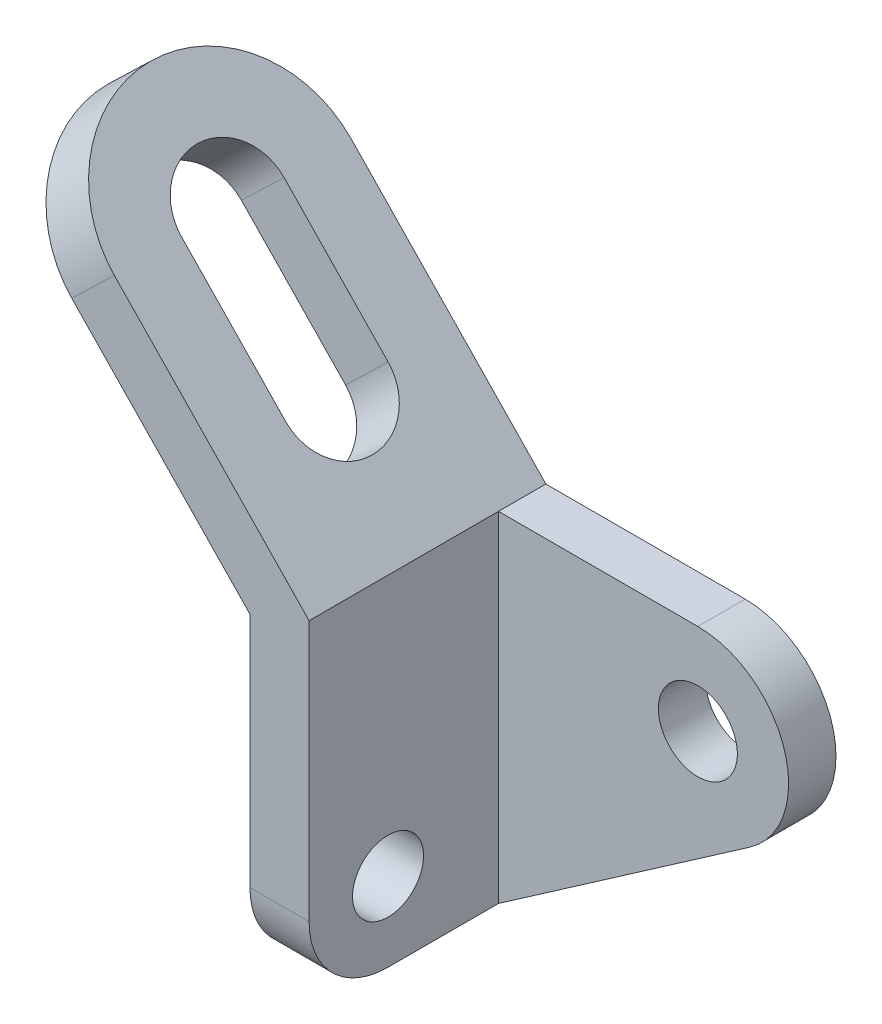
SolidWorks part; units mm, degrees
ref_plane "정면" through (0, 0, 0) normal (0, 0, 1) x (1, 0, 0)
ref_plane "윗면" through (0, 0, 0) normal (0, 1, 0) x (1, 0, 0)
ref_plane "우측면" through (0, 0, 0) normal (1, 0, 0) x (0, 0, -1)
sketch "스케치1" plane through (0, 0, 0) normal (0, 0, 1) x (1, 0, 0)
  line L0 (-22.8432, 40.2912) -> (43.1493, -28.0461)
  line L1 (43.1493, -28.0461) -> (43.1493, -108.0461)
  line L2 (-12.0531, 50.7111) -> (58.1493, -21.9857)
  line L3 (58.1493, -21.9857) -> (58.1493, -108.0461)
  line L4 (-22.8432, 40.2912) -> (-12.0531, 50.7111)
  line L5 (43.1493, -108.0461) -> (58.1493, -108.0461)
  dimension "D1" = 136
  dimension "D3" = 95
  dimension "D4" = 80
  dimension "D2" = 15
extrude "보스-돌출1" add sketch "스케치1" along normal blind 60
fillet "필렛1" radius 30 2 edges at (-17.4482, 45.5011, 0) (-17.4482, 45.5011, 60)
sketch "스케치2" plane through (19.1032, 18.4477, 0) normal (0.7193, 0.6947, 0) x (0, 0, -1)
  line L0 (-30, 14.8513) -> (-30, -23.1487) construction
  line L1 (-17, 14.8513) -> (-17, -23.1487)
  line L2 (-43, 14.8513) -> (-43, -23.1487)
  arc A0 (-17, 14.8513) -> (-43, 14.8513) centre (-30, 14.8513) ccw
  arc A1 (-43, -23.1487) -> (-17, -23.1487) centre (-30, -23.1487) ccw
  arc A2 (-30, 44.8513) -> (-60, 14.8513) centre (-30, 14.8513) ccw construction
  point P2 (-30, -4.1487)
  dimension "D1" = 13
  dimension "D2" = 38
extrude "컷-돌출1" cut sketch "스케치2" against normal through all contours L2 A1 L1 A0 region at (21.9851, 15.4634, 30)
sketch "스케치4" plane through (0, 0, 0) normal (0, 0, -1) x (-1, 0, 0)
  line L0 (-58.1493, -21.9857) -> (-108.6742, -21.9857)
  line L1 (-58.1493, -108.0461) -> (-121.7876, -63.8812)
  arc A0 (-121.7876, -63.8812) -> (-108.6742, -21.9857) centre (-108.6742, -44.9857) cw
  circle A1 centre (-108.6742, -44.9857) radius 10
  line M4 (-58.1493, -21.9857) -> (-58.1493, -108.0461)
  dimension "D1" = 23
  dimension "D2" = 20
extrude "보스-돌출3" add sketch "스케치4" against normal blind 12 contours A0 L1 L0 A1 M4 region at (87.0021, -55.5162, 0)
fillet "필렛2" radius 20 1 edges at (50.6493, -108.0461, 60)
sketch "스케치5" plane through (58.1493, 0, 0) normal (1, 0, 0) x (0, 0, -1)
  circle A0 centre (-40, -88.0461) radius 9
  dimension "D1" = 18
extrude "컷-돌출3" cut sketch "스케치5" against normal blind 15 contours A0
